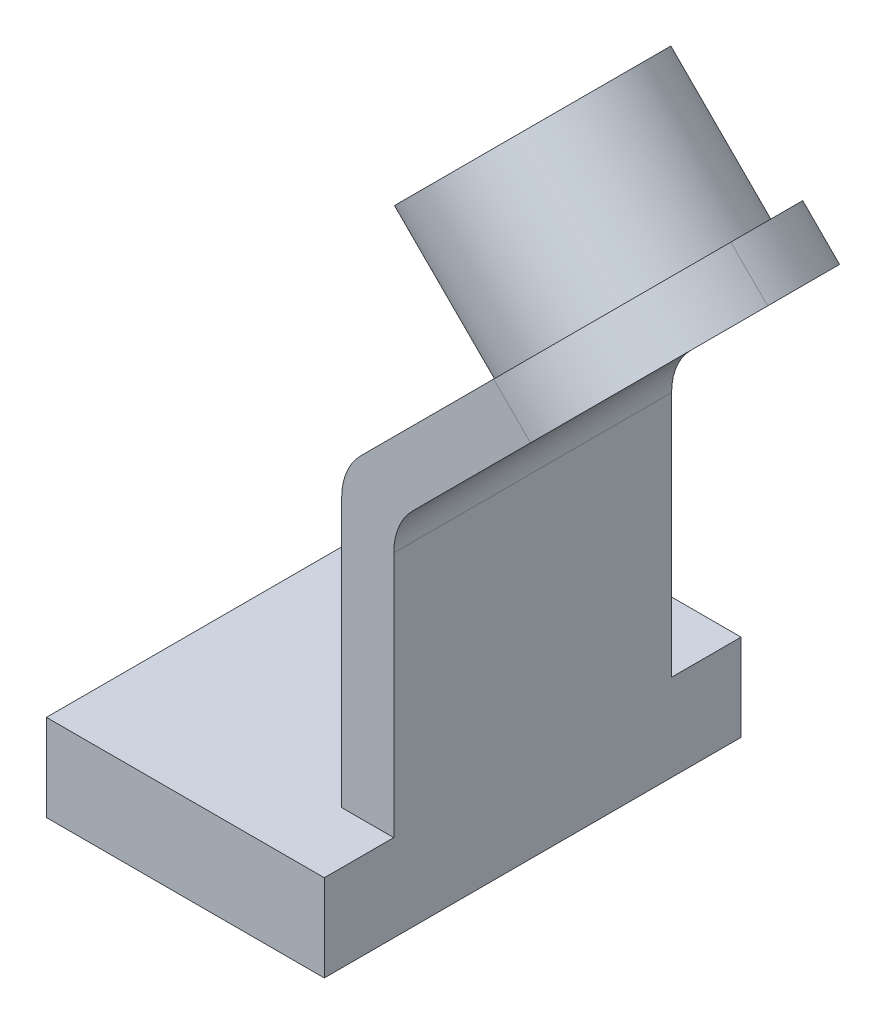
SolidWorks part; units mm, degrees
ref_plane "Front Plane" through (0, 0, 0) normal (0, 0, 1) x (1, 0, 0)
ref_plane "Top Plane" through (0, 0, 0) normal (0, 1, 0) x (1, 0, 0)
ref_plane "Right Plane" through (0, 0, 0) normal (1, 0, 0) x (0, 0, -1)
sketch "Sketch1" plane through (0, 0, 0) normal (0, 0, 1) x (1, 0, 0)
  line L0 (32, 10) -> (32, 73)
  line L1 (-32, -10) -> (32, -10)
  line L2 (-32, -10) -> (-32, 10)
  line L3 (-32, 10) -> (32, 10)
  line L4 (32, -10) -> (32, 10)
  line L5 (-32, -10) -> (32, 10) construction
  line L6 (-32, 10) -> (32, -10) construction
  line L7 (32, 73) -> (86.1274, 127.1274)
  line L8 (55.0147, 112.9853) -> (88.7441, 79.2559) construction
  line L9 (32, 10) -> (32, 136) construction
  line L10 (32, 136) -> (-32, 136) construction
  line L11 (-32, 136) -> (-32, 10) construction
  line L12 (20, 10) -> (20, 77.9706)
  line L13 (20, 77.9706) -> (77.6421, 135.6127)
  line L14 (32, 10) -> (20, 10)
  line L15 (86.1274, 127.1274) -> (77.6421, 135.6127)
  line L17 (55.0147, 112.9853) -> (73.3995, 131.3701)
  line L18 (73.3995, 131.3701) -> (50.3848, 154.3848)
  line L19 (50.3848, 154.3848) -> (43.3137, 147.3137)
  line L20 (32, 136) -> (55.0147, 112.9853)
  line L21 (32, 136) -> (55.0147, 112.9853) construction
  line L22 (43.3137, 147.3137) -> (66.3284, 124.299)
  point P0 (0, 0)
  dimension "D1" = 20
  dimension "D2" = 64
  dimension "D3" = 45
  dimension "D4" = 146
  dimension "D5" = 12
  dimension "D6" = 26
  dimension "D7" = 6
  dimension "D8" = 16
extrude "Boss-Extrude1" add sketch "Sketch1" along normal mid plane 96 contours L1 L4 L3 L2 region at (0, 0, 0)
extrude "Boss-Extrude2" add sketch "Sketch1<3>" along normal mid plane 64 contours L7 L15 L13 L12 L3 L0 region at (26, 11.4196, 0)
sketch "Sketch1<3>" plane through (0, 0, 0) normal (0, 0, 1) x (1, 0, 0) same geometry as "Sketch1"
fillet "Fillet2" radius 32 2 edges at (81.8848, 131.3701, -32) (81.8848, 131.3701, 32)
fillet "Fillet3" radius 15 2 edges at (20, 77.9706, 0) (32, 73, 0)
revolve "Revolve3" add sketch "Sketch1<5>" angle 360 about L20 region at (58.3566, 139.3419, 0)
sketch "Sketch1<5>" plane through (0, 0, 0) normal (0, 0, 1) x (1, 0, 0) same geometry as "Sketch1"
